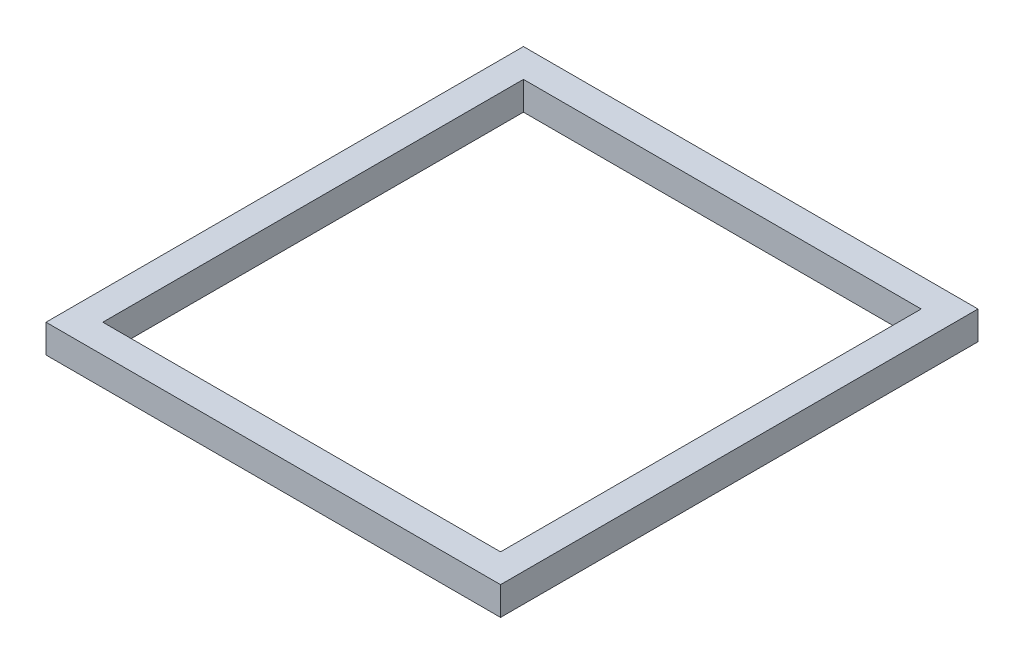
SolidWorks part; units mm, degrees
material "Silicon Rubber"
ref_plane "Front Plane" through (0, 0, 0) normal (0, 0, 1) x (1, 0, 0)
ref_plane "Top Plane" through (0, 0, 0) normal (0, 1, 0) x (1, 0, 0)
ref_plane "Right Plane" through (0, 0, 0) normal (1, 0, 0) x (0, 0, -1)
sketch "Sketch1" plane through (0, 0, 0) normal (0, 1, 0) x (1, 0, 0)
  line L1 (0, 0) -> (25.4, 0)
  line L2 (0, 0) -> (0, 26.68)
  line L3 (0, 26.68) -> (25.4, 26.68)
  line L4 (25.4, 0) -> (25.4, 26.68)
  line L5 (1.5875, 1.5875) -> (23.8125, 1.5875)
  line L6 (1.5875, 1.5875) -> (1.5875, 25.0925)
  line L7 (1.5875, 25.0925) -> (23.8125, 25.0925)
  line L8 (23.8125, 1.5875) -> (23.8125, 25.0925)
  dimension "D1" = 1.5875
  dimension "D2" = 1.5875
  dimension "D3" = 1.5875
  dimension "D4" = 1.5875
  dimension "D5" = 25.4
  dimension "D6" = 26.68
extrude "Boss-Extrude1" add sketch "Sketch1" along normal blind 1.5875
